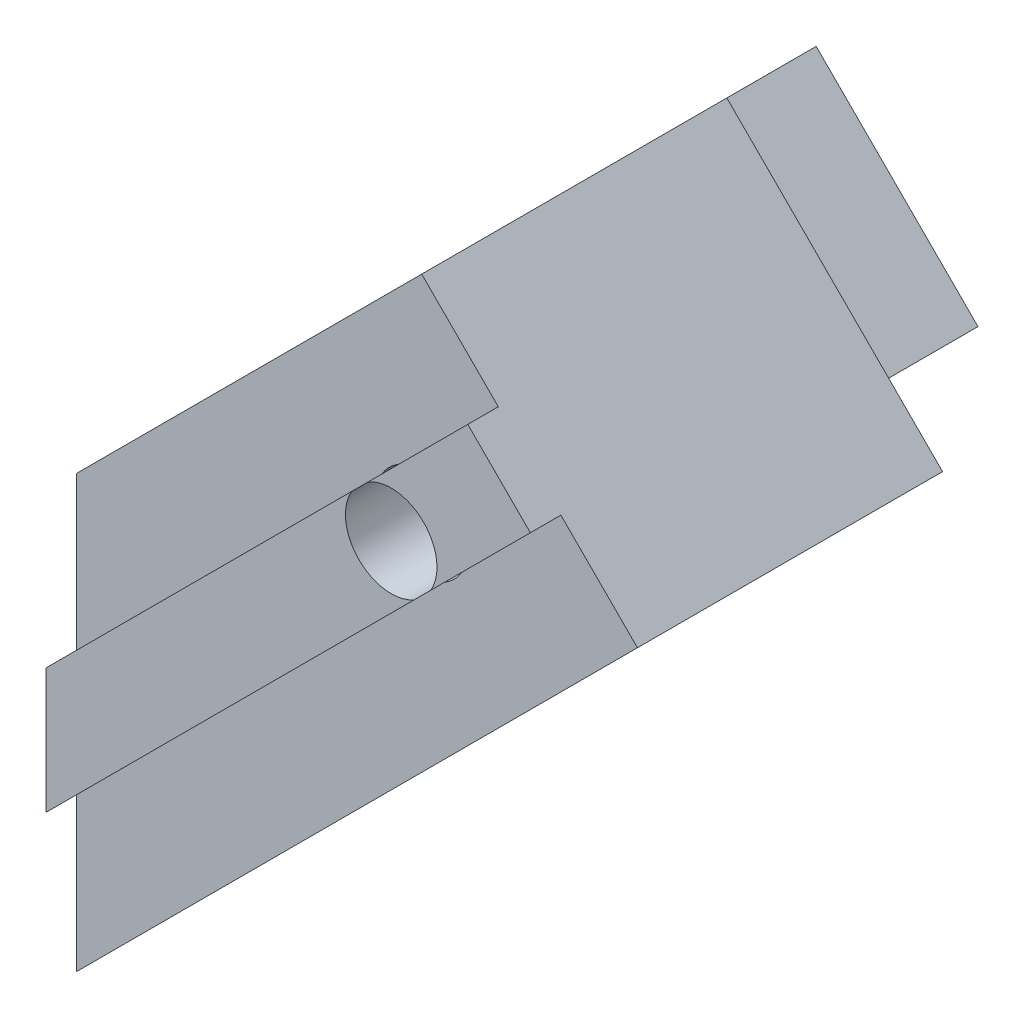
SolidWorks part; units mm, degrees
ref_plane "Front Plane" through (0, 0, 0) normal (0, 0, 1) x (1, 0, 0)
ref_plane "Top Plane" through (0, 0, 0) normal (0, 1, 0) x (1, 0, 0)
ref_plane "Right Plane" through (0, 0, 0) normal (1, 0, 0) x (0, 0, -1)
sketch "Esquisse1" plane through (0, 0, 0) normal (0, 0, 1) x (1, 0, 0)
  line L0 (0, 0) -> (0, 5)
  line L1 (0, 5) -> (-1, 5)
  line L2 (-1, 5) -> (-1, 7.9)
  line L3 (-1, 7.9) -> (0, 7.9)
  line L4 (0, 7.9) -> (0, 14.1421)
  line L5 (0, 14.1421) -> (11.3137, 25.4558)
  line L6 (11.3137, 25.4558) -> (18.3848, 18.3848)
  line L7 (18.3848, 18.3848) -> (0, 0)
  point P5 (1.7731, -7.0523)
  point P10 (1.9221, 9.7845)
  point P11 (0, 6.2085)
  point P12 (0, 0)
  point P13 (0, 0)
  point P15 (16.9162, 21.1191)
  dimension "D1" = 2.9
  dimension "D2" = 45
  dimension "D3" = 10
  dimension "D4" = 5
  dimension "D5" = 1
  dimension "D6" = 26
extrude "Boss.-Extru.1" add sketch "Esquisse1" along normal blind 20
sketch "Esquisse2" plane through (0, 0, 0) normal (0.7071, -0.7071, 0) x (0, 0, -1)
  line L0 (0, 0) -> (0, 26) construction
  line L1 (-10, 5) -> (0, 5)
  line L2 (-10, 5) -> (-10, 26)
  line L3 (-10, 26) -> (0, 26)
  line L4 (0, 5) -> (0, 26)
  line L5 (-20, 26) -> (0, 26) construction
  line L6 (-20, 0) -> (0, 0) construction
  dimension "D1" = 5
  dimension "D2" = 10
extrude "Enlèv. mat.-Extru.1" cut sketch "Esquisse2" against normal blind 2.5
sketch "Esquisse3" plane through (-1, 0, 0) normal (-1, 0, 0) x (0, 0, 1)
  line L0 (20, 7.9) -> (20, 5) construction
  line L2 (20, 7.9) -> (0, 7.9) construction
  circle A0 centre (15, 6.45) radius 1.5
  point P2 (0, 0)
  point P5 (20, 6.45)
  point P6 (9.1439, 9.1421)
  point P7 (0, 0)
  point P10 (10, 7.9)
  point P11 (0, 0)
  dimension "D1" = 3
  dimension "D2" = 5
extrude "Enlèv. mat.-Extru.2" cut sketch "Esquisse3" against normal through all
ref_plane "Plan1" through (3, 0, 0) normal (-1, 0, 0) x (0, 0, 1)
sketch "Esquisse4" plane through (3, 0, 0) normal (-1, 0, 0) x (0, 0, 1)
  circle A0 centre (15, 6.45) radius 4
  arc A1 (15.3841, 5) -> (15.3841, 7.9) centre (15, 6.45) ccw construction
  dimension "D1" = 8
extrude "Enlèv. mat.-Extru.3" cut sketch "Esquisse4" against normal through all
sketch "Esquisse5" plane through (-1.7678, 1.7678, 0) normal (0.7071, -0.7071, 0) x (0, 0, -1)
  line L0 (0, 26) -> (-10, 26) construction
  line L1 (0, 5) -> (0, 26) construction
  line L2 (-10, 5) -> (0, 5) construction
  circle A0 centre (-5, 11.5) radius 1.25
  point P4 (-5, 26)
  point P5 (0, 0)
  point P8 (0, 15.5)
  point P9 (-4.3391, 17.5)
  dimension "D1" = 2.5
  dimension "D2" = 6.5
extrude "Enlèv. mat.-Extru.4" cut sketch "Esquisse5" against normal through all
sketch "Esquisse6" plane through (0, 0, 20) normal (0, 0, 1) x (1, 0, 0)
  line L0 (0, 9.1217) -> (13.8239, 22.9456)
  line L1 (18.3848, 18.3848) -> (11.3137, 25.4558) construction
  line L2 (13.8239, 22.9456) -> (15.8745, 20.895)
  line L3 (15.8745, 20.895) -> (0, 5.0205)
  line L4 (0, 5.0205) -> (0, 9.1217)
  line L5 (0, 5) -> (0, 0) construction
  point P6 (14.8492, 21.9203)
  point P7 (14.8492, 21.9203)
  dimension "D1" = 2.9
extrude "Boss.-Extru.2" add sketch "Esquisse6" along normal blind 1
ref_plane "Plan2" through (-3.5355, 3.5355, 0) normal (0.7071, -0.7071, 0) x (0, 0, -1)
sketch "Esquisse7" plane through (0, 0, 21) normal (0, 0, 1) x (1, 0, 0)
  line L0 (-11.3137, -4.2426) -> (4.2426, 11.3137) construction
  line L1 (15.8745, 20.895) -> (13.8239, 22.9456) construction
  circle A0 centre (11.3137, 18.3848) radius 1.5
  point P2 (0, 0)
  point P3 (0, 0)
  dimension "D1" = 3
  dimension "D2" = 5
extrude "Enlèv. mat.-Extru.5" cut sketch "Esquisse7" against normal through all
ref_plane "Plan3" through (0, 0, 17) normal (0, 0, 1) x (1, 0, 0)
sketch "Esquisse8" plane through (0, 0, 17) normal (0, 0, 1) x (1, 0, 0)
  circle A0 centre (11.3137, 18.3848) radius 4
  arc A1 (10.0168, 19.1385) -> (12.0674, 17.0879) centre (11.3137, 18.3848) ccw construction
  dimension "D1" = 8
extrude "Enlèv. mat.-Extru.6" cut sketch "Esquisse8" against normal through all
sketch "Esquisse9" plane through (0, 0, 10) normal (0, 0, -1) x (-1, 0, 0)
  line L0 (-18.3848, 18.3848) -> (-12.0208, 12.0208)
  line L1 (-18.3848, 18.3848) -> (-3.5355, 3.5355) construction
  line L2 (-12.0208, 12.0208) -> (-4.9497, 19.0919)
  line L3 (-4.9497, 19.0919) -> (-11.3137, 25.4558)
  line L5 (-11.3137, 25.4558) -> (-18.3848, 18.3848)
  point P7 (-11.4149, 25.3547)
  point P8 (-11.4568, 25.3127)
  point P9 (0, 0)
  dimension "D1" = 9
extrude "Enlèv. mat.-Extru.7" cut sketch "Esquisse9" along normal through all
sketch "Esquisse10" plane through (0, 0, 10) normal (0, 0, -1) x (-1, 0, 0)
  line L0 (-11.3137, 25.4558) -> (-4.2426, 18.3848)
  line L1 (-4.2426, 18.3848) -> (-11.3137, 11.3137)
  line L2 (-18.3848, 18.3848) -> (-3.5355, 3.5355) construction
  line L3 (-11.3137, 11.3137) -> (-18.3848, 18.3848)
  line L4 (-18.3848, 18.3848) -> (-11.3137, 25.4558)
  point P9 (0, 0)
  point P10 (0, 0)
  point P11 (-3.5886, 17.6777)
  dimension "D1" = 10
extrude "Enlèv. mat.-Extru.8" cut sketch "Esquisse10" along normal through all
sketch "Esquisse11" plane through (-4.1213, 2.9497, 0) normal (-0.7071, 0.7071, 0) x (0, 0, 1)
  circle A0 centre (5, 12.3284) radius 4
  circle A1 centre (5, 12.3284) radius 1.25 construction
  dimension "D1" = 8
extrude "Enlèv. mat.-Extru.11" cut sketch "Esquisse11" along normal through all
